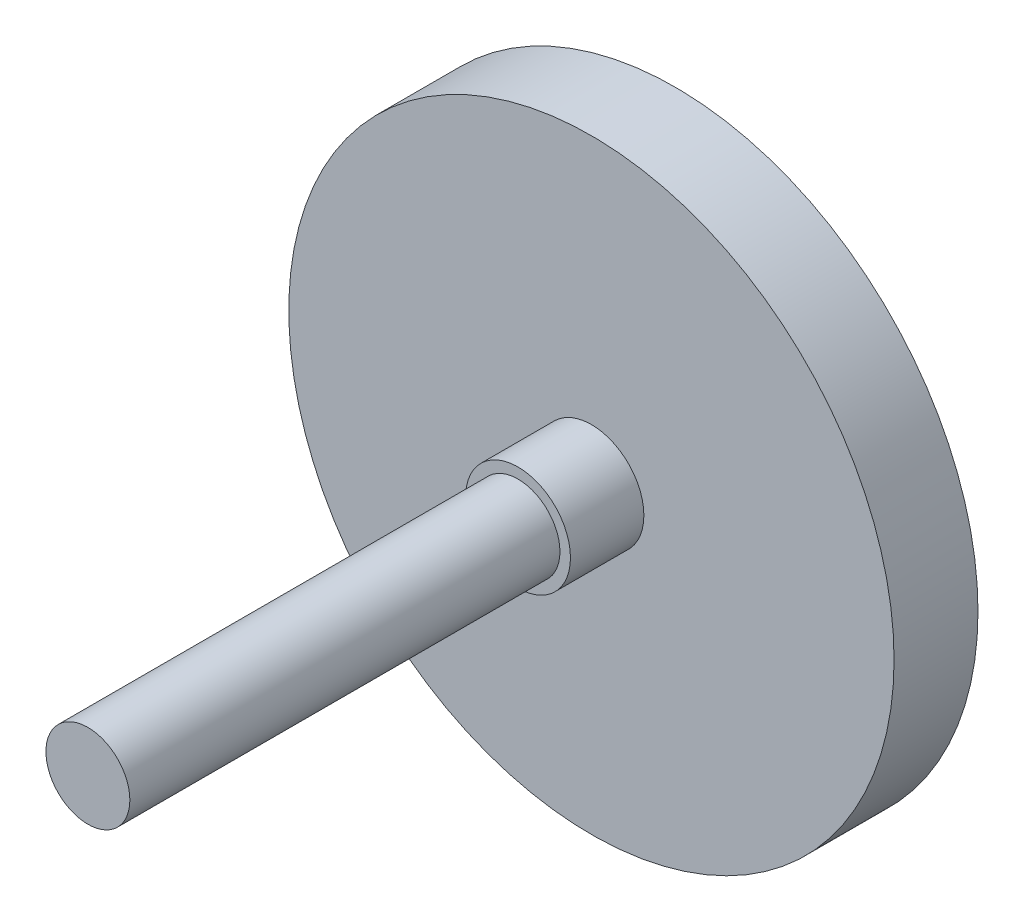
SolidWorks part; units mm, degrees
ref_plane "Plan de face" through (0, 0, 0) normal (0, 0, 1) x (1, 0, 0)
ref_plane "Plan de dessus" through (0, 0, 0) normal (0, 1, 0) x (1, 0, 0)
ref_plane "Plan de droite" through (0, 0, 0) normal (1, 0, 0) x (0, 0, -1)
sketch "Esquisse1" plane through (0, 0, 0) normal (0, 0, 1) x (1, 0, 0)
  circle A0 centre (0, 0) radius 28.85
extrude "Boss.-Extru.1" add sketch "Esquisse1" along normal blind 8
sketch "Esquisse2" plane through (0, 0, 8) normal (0, 0, 1) x (1, 0, 0)
  circle A0 centre (0, 0) radius 4
  circle A1 centre (0, 0) radius 5
sketch "Esquisse3" plane through (0, 0, 0) normal (0, 0, -1) x (-1, 0, 0)
  circle A0 centre (0, 0) radius 4
extrude "Enlèv. mat.-Extru.1" cut sketch "Esquisse3" against normal blind 2
extrude "Boss.-Extru.2" add sketch "Esquisse2" along normal blind 7
extrude "Boss.-Extru.3" add sketch "Esquisse2<2>" along normal blind 2
sketch "Esquisse2<2>" plane through (0, 0, 8) normal (0, 0, 1) x (1, 0, 0) same geometry as "Esquisse2"
extrude "Boss.-Extru.4" add sketch "Esquisse2<3>" along normal blind 4
sketch "Esquisse2<3>" plane through (0, 0, 8) normal (0, 0, 1) x (1, 0, 0) same geometry as "Esquisse2"
sketch "Esquisse4" plane through (0, 0, 8) normal (0, 0, 1) x (1, 0, 0)
  circle A0 centre (0, 0) radius 4
extrude "Boss.-Extru.6" add sketch "Esquisse4" along normal blind 48
